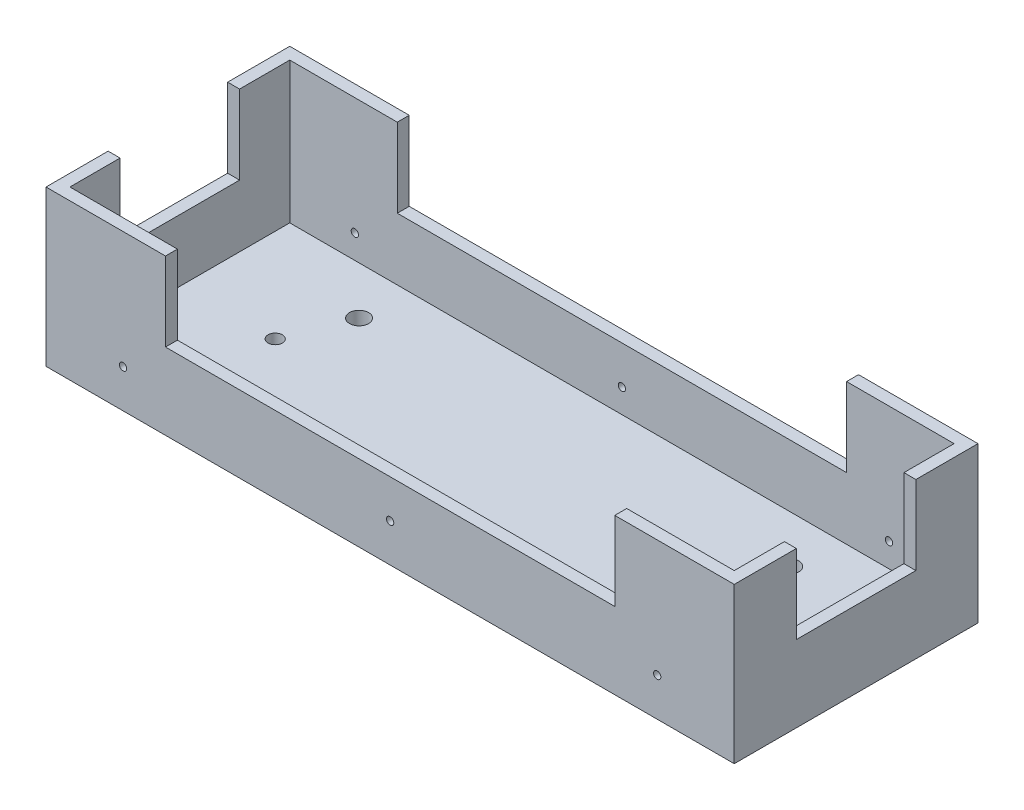
SolidWorks part; units mm, degrees
ref_plane "Front Plane" through (0, 0, 0) normal (0, 0, 1) x (1, 0, 0)
ref_plane "Top Plane" through (0, 0, 0) normal (0, 1, 0) x (1, 0, 0)
ref_plane "Right Plane" through (0, 0, 0) normal (1, 0, 0) x (0, 0, -1)
sketch "Sketch1" plane through (0, 0, 0) normal (0, 1, 0) x (1, 0, 0)
  line L1 (72, 25.5) -> (-72, 25.5)
  line L2 (72, 25.5) -> (72, -25.5)
  line L3 (72, -25.5) -> (-72, -25.5)
  line L4 (-72, 25.5) -> (-72, -25.5)
  line L5 (72, 25.5) -> (-72, -25.5) construction
  line L6 (72, -25.5) -> (-72, 25.5) construction
  point P0 (0, 0)
  dimension "D1" = 144
  dimension "D2" = 51
extrude "Boss-Extrude1" add sketch "Sketch1" along normal blind 3
sketch "Sketch2" plane through (0, 3, 0) normal (0, 1, 0) x (1, 0, 0)
  line L1 (72, 25.5) -> (-72, 25.5)
  line L2 (72, 25.5) -> (72, -25.5)
  line L3 (72, -25.5) -> (-72, -25.5)
  line L4 (-72, 25.5) -> (-72, -25.5)
  line L5 (72, 25.5) -> (-72, -25.5) construction
  line L6 (72, -25.5) -> (-72, 25.5) construction
  line L7 (69.5, -23) -> (-69.5, -23)
  line L8 (69.5, -23) -> (69.5, 23)
  line L9 (69.5, 23) -> (-69.5, 23)
  line L10 (-69.5, -23) -> (-69.5, 23)
  line L11 (69.5, -23) -> (-69.5, 23) construction
  line L12 (69.5, 23) -> (-69.5, -23) construction
  point P0 (0, 0)
  point P7 (0, 0)
  dimension "D1" = 2.5
  dimension "D2" = 2.5
extrude "Boss-Extrude2" add sketch "Sketch2" along normal blind 16 from surface starting at face at (0, 0, 0)
sketch "Sketch3" plane through (0, 16, 0) normal (0, 1, 0) x (1, 0, 0)
  line L0 (0, 25.5) -> (0, -25.5) construction
  line L1 (-72, 25.5) -> (72, 25.5) construction
  line L2 (72, -25.5) -> (-72, -25.5) construction
  line L3 (-72, 0) -> (72, 0) construction
  line L4 (-72, -25.5) -> (-72, 25.5) construction
  line L5 (72, 25.5) -> (72, -25.5) construction
  line L6 (-72, 25.5) -> (-72, 12.5)
  line L7 (-72, 12.5) -> (-69.5, 12.5)
  line L8 (-69.5, -23) -> (-69.5, 23) construction
  line L9 (-69.5, 12.5) -> (-69.5, 23)
  line L10 (-69.5, 23) -> (-47, 23)
  line L11 (-69.5, 23) -> (69.5, 23) construction
  line L12 (-47, 23) -> (-47, 25.5)
  line L13 (-47, 25.5) -> (-72, 25.5)
  line L14 (47, 25.5) -> (72, 25.5)
  line L15 (47, 23) -> (47, 25.5)
  line L16 (69.5, 23) -> (47, 23)
  line L17 (69.5, 12.5) -> (69.5, 23)
  line L18 (72, 12.5) -> (69.5, 12.5)
  line L19 (72, 25.5) -> (72, 12.5)
  line L20 (72, -25.5) -> (72, -12.5)
  line L21 (72, -12.5) -> (69.5, -12.5)
  line L22 (69.5, -12.5) -> (69.5, -23)
  line L23 (69.5, -23) -> (47, -23)
  line L24 (47, -23) -> (47, -25.5)
  line L25 (47, -25.5) -> (72, -25.5)
  line L26 (-47, -25.5) -> (-72, -25.5)
  line L27 (-47, -23) -> (-47, -25.5)
  line L28 (-69.5, -23) -> (-47, -23)
  line L29 (-69.5, -12.5) -> (-69.5, -23)
  line L30 (-72, -12.5) -> (-69.5, -12.5)
  line L31 (-72, -25.5) -> (-72, -12.5)
  dimension "D1" = 13
  dimension "D2" = 25
extrude "Boss-Extrude3" add sketch "Sketch3" along normal blind 16.5
sketch "Sketch4" plane through (0, 0, 0) normal (0, -1, 0) x (1, 0, 0)
  line L0 (-72, 0) -> (72, 0) construction
  line L1 (-72, -25.5) -> (-72, 25.5) construction
  line L2 (72, 25.5) -> (72, -25.5) construction
  line L3 (-45, 25.5) -> (-45, -25.5) construction
  line L4 (-72, 25.5) -> (72, 25.5) construction
  line L5 (72, -25.5) -> (-72, -25.5) construction
  line L6 (-47, -25.5) -> (-72, -25.5) construction
  line L7 (0, 25.5) -> (0, -25.5) construction
  line L8 (45, 25.5) -> (45, -25.5) construction
  circle A0 centre (-45, -13) radius 2
  circle A1 centre (-45, 13) radius 2
  circle A2 centre (45, 13) radius 2
  circle A3 centre (45, -13) radius 2
  circle A4 centre (-50, -0.45) radius 1.5
  circle A5 centre (50, -0.45) radius 1.5
  point P16 (-59.5, -25.5)
  point P19 (-47, 13)
  point P28 (47, 13)
  dimension "D3" = 4
  dimension "D7" = 3
  dimension "D1" = 12.5
  dimension "D2" = 12.5
  dimension "D4" = 25
  dimension "D5" = 22
  dimension "D6" = 25.05
extrude "Cut-Extrude1" cut sketch "Sketch4" against normal through all
sketch "Sketch5" plane through (0, 0, 25.5) normal (0, 0, 1) x (1, 0, 0)
  line L0 (-55.88, 8) -> (0, 8) construction
  line L1 (0, 8) -> (55.88, 8) construction
  line L2 (0, 8) -> (0, 0) construction
  line L3 (0, 8) -> (0, 16) construction
  line L4 (47, 16) -> (-47, 16) construction
  circle A0 centre (-55.88, 8) radius 0.762
  circle A1 centre (55.88, 8) radius 0.762
  circle A2 centre (0, 8) radius 0.762
  dimension "D1" = 1.524
  dimension "D2" = 55.88
extrude "Cut-Extrude2" cut sketch "Sketch5" against normal through all
equation "\"D2@Sketch4\"=\"D1@Sketch4\""
